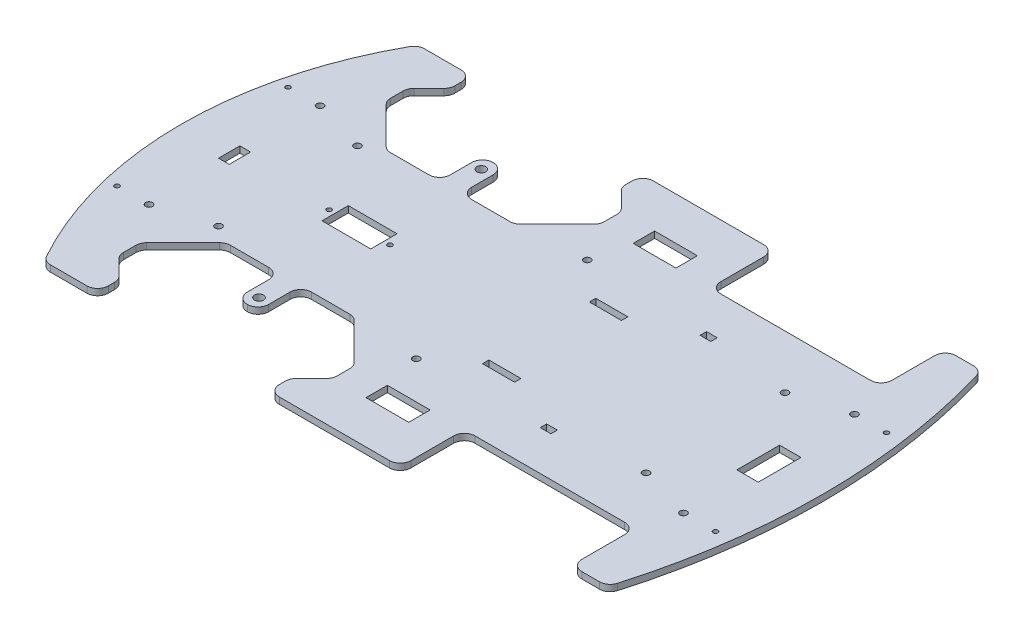
SolidWorks part; units mm, degrees
ref_plane "Front Plane" through (0, 0, 0) normal (0, 0, 1) x (1, 0, 0)
ref_plane "Top Plane" through (0, 0, 0) normal (0, 1, 0) x (1, 0, 0)
ref_plane "Right Plane" through (0, 0, 0) normal (1, 0, 0) x (0, 0, -1)
sketch "Sketch1" plane through (0, 0, 0) normal (0, 1, 0) x (1, 0, 0)
  line L1 (-150, -87.5) -> (150, -87.5) construction
  line L2 (-150, -87.5) -> (-150, 87.5) construction
  line L3 (-150, 87.5) -> (150, 87.5) construction
  line L4 (150, -87.5) -> (150, 87.5) construction
  line L5 (-150, -87.5) -> (150, 87.5) construction
  line L6 (-150, 87.5) -> (150, -87.5) construction
  line L7 (-91.537, 37.4826) -> (-31.537, 37.4826) construction
  line L9 (40, 87.5) -> (40, 57.5)
  line L10 (40, 57.5) -> (120, 57.5)
  line L11 (120, 57.5) -> (120, 87.5)
  line L12 (-150, 0) -> (150, 0) construction
  line L13 (-126.5544, 87.5) -> (-101.5544, 87.5)
  line L14 (120, -57.5) -> (120, -87.5)
  line L15 (-77.937, -6.15) -> (-55.137, -6.15)
  line L16 (-77.937, -6.15) -> (-77.937, 6.15)
  line L17 (-77.937, 6.15) -> (-55.137, 6.15)
  line L18 (-55.137, -6.15) -> (-55.137, 6.15)
  line L19 (-77.937, -6.15) -> (-55.137, 6.15) construction
  line L20 (-77.937, 6.15) -> (-55.137, -6.15) construction
  line L21 (40, -57.5) -> (120, -57.5)
  line L22 (40, -87.5) -> (40, -57.5)
  line L24 (-91.537, -37.4826) -> (-31.537, -37.4826) construction
  line L26 (-61.537, 37.4826) -> (-61.537, -37.4826) construction
  line L27 (-66.537, 6.15) -> (-66.537, -6.15) construction
  line L28 (-66.537, 37.4826) -> (-66.537, 57.4826)
  line L29 (-66.537, 57.4826) -> (-56.537, 57.4826)
  line L30 (-56.537, 57.4826) -> (-56.537, 37.4826)
  line L31 (-91.537, 37.4826) -> (-66.537, 37.4826)
  line L32 (-56.537, 37.4826) -> (-31.537, 37.4826)
  line L35 (-56.537, -57.4826) -> (-56.537, -37.4826)
  line L36 (-66.537, -57.4826) -> (-56.537, -57.4826)
  line L37 (-66.537, -37.4826) -> (-66.537, -57.4826)
  line L45 (80, 57.5) -> (80, -57.5) construction
  line L47 (40, 87.5) -> (-21.5544, 87.5)
  line L57 (-101.5544, 87.5) -> (-101.5544, 77.5)
  line L58 (-101.5544, 77.5) -> (-111.5544, 67.5)
  line L59 (-111.5544, 67.5) -> (-111.5544, 57.5)
  line L62 (-21.5544, 87.5) -> (-21.5544, 77.5)
  line L63 (-21.5544, 77.5) -> (-11.5544, 67.5)
  line L64 (-11.5544, 67.5) -> (-11.5544, 57.4651)
  line L65 (-11.5544, 57.4651) -> (-31.537, 37.4826)
  line L66 (-111.5544, 57.5) -> (-91.537, 37.4826)
  line L67 (-126.5544, -87.5) -> (-101.5544, -87.5)
  line L68 (-101.5544, -87.5) -> (-101.5544, -77.5)
  line L69 (-101.5544, -77.5) -> (-111.5544, -67.5)
  line L70 (-111.5544, -67.5) -> (-111.5544, -57.5)
  line L71 (-111.5544, -57.5) -> (-91.537, -37.4826)
  line L72 (-91.537, -37.4826) -> (-66.537, -37.4826)
  line L73 (-56.537, -37.4826) -> (-31.537, -37.4826)
  line L74 (-11.5544, -57.4651) -> (-31.537, -37.4826)
  line L75 (-11.5544, -67.5) -> (-11.5544, -57.4651)
  line L76 (-21.5544, -77.5) -> (-11.5544, -67.5)
  line L77 (-21.5544, -87.5) -> (-21.5544, -77.5)
  line L78 (40, -87.5) -> (-21.5544, -87.5)
  line L79 (120, -87.5) -> (136.956, -87.5)
  line L80 (120, 87.5) -> (136.956, 87.5)
  line L81 (56.9, -35.9) -> (61.9, -38.9) construction
  line L82 (56.9, 38.9) -> (61.9, 38.9)
  line L83 (56.9, 38.9) -> (56.9, 35.9)
  line L84 (56.9, 35.9) -> (61.9, 35.9)
  line L85 (61.9, 38.9) -> (61.9, 35.9)
  line L86 (56.9, 38.9) -> (61.9, 35.9) construction
  line L87 (56.9, 35.9) -> (61.9, 38.9) construction
  line L88 (56.9, -38.9) -> (61.9, -35.9) construction
  line L89 (61.9, -38.9) -> (61.9, -35.9)
  line L90 (56.9, -35.9) -> (61.9, -35.9)
  line L91 (56.9, -38.9) -> (56.9, -35.9)
  line L92 (56.9, -38.9) -> (61.9, -38.9)
  line L93 (0, 87.5) -> (0, -87.5) construction
  line L94 (17.5, -23.5) -> (32.5, -26.5) construction
  line L95 (120, -10) -> (130, -10)
  line L96 (120, -10) -> (120, 10)
  line L97 (120, 10) -> (130, 10)
  line L98 (130, -10) -> (130, 10)
  line L99 (120, -10) -> (130, 10) construction
  line L100 (120, 10) -> (130, -10) construction
  line L101 (17.5, 23.5) -> (32.5, 23.5)
  line L102 (17.5, 23.5) -> (17.5, 26.5)
  line L103 (17.5, 26.5) -> (32.5, 26.5)
  line L104 (32.5, 23.5) -> (32.5, 26.5)
  line L105 (17.5, 23.5) -> (32.5, 26.5) construction
  line L106 (17.5, 26.5) -> (32.5, 23.5) construction
  line L107 (17.5, -26.5) -> (32.5, -23.5) construction
  line L108 (17.5, -26.5) -> (32.5, -26.5)
  line L109 (32.5, -23.5) -> (32.5, -26.5)
  line L110 (17.5, -23.5) -> (32.5, -23.5)
  line L111 (17.5, -23.5) -> (17.5, -26.5)
  line L112 (4, -67.5) -> (24, -57.5) construction
  line L117 (4, 57.5) -> (24, 57.5)
  line L118 (4, 57.5) -> (4, 67.5)
  line L119 (4, 67.5) -> (24, 67.5)
  line L124 (24, 57.5) -> (24, 67.5)
  line L125 (4, 57.5) -> (24, 67.5) construction
  line L126 (4, 67.5) -> (24, 57.5) construction
  line L127 (4, -57.5) -> (24, -67.5) construction
  line L128 (4, -67.5) -> (24, -67.5)
  line L129 (24, -57.5) -> (24, -67.5)
  line L130 (4, -57.5) -> (24, -57.5)
  line L131 (4, -57.5) -> (4, -67.5)
  line L133 (-127.5, -5) -> (-122.5, -5)
  line L134 (-127.5, -5) -> (-127.5, 5)
  line L135 (-127.5, 5) -> (-122.5, 5)
  line L136 (-122.5, -5) -> (-122.5, 5)
  line L137 (-127.5, -5) -> (-122.5, 5) construction
  line L138 (-127.5, 5) -> (-122.5, -5) construction
  circle A0 centre (-80.787, 0) radius 1.1
  circle A1 centre (-52.287, 0) radius 1.1
  circle A3 centre (-61.537, 52) radius 2.1
  circle A4 centre (-61.537, -52) radius 2.1
  arc A7 (-126.5544, 87.5) -> (-126.5544, -87.5) centre (25, 0) ccw
  arc A10 (136.956, 87.5) -> (136.956, -87.5) centre (-150, 0) cw
  circle A11 centre (-100, 32.5) radius 1.6
  circle A12 centre (100, 32.5) radius 1.6
  circle A13 centre (100, -32.5) radius 1.6
  circle A14 centre (-100, -32.5) radius 1.6
  circle A15 centre (-125, -40) radius 1.6
  circle A16 centre (0, -40) radius 1.6
  circle A17 centre (125, -40) radius 1.6
  circle A18 centre (125, 40) radius 1.6
  circle A19 centre (0, 40) radius 1.6
  circle A20 centre (-125, 40) radius 1.6
  circle A21 centre (-140, 40) radius 1.1
  circle A22 centre (140, 40) radius 1.1
  circle A23 centre (-140, -40) radius 1.1
  circle A24 centre (140, -40) radius 1.1
  point P0 (0, 0)
  point P18 (-66.537, 0)
  point P53 (59.4, 37.4)
  point P79 (59.4, -37.4)
  point P101 (25, 25)
  point P103 (125, 0)
  point P111 (25, -25)
  point P116 (14, 62.5)
  point P127 (14, -62.5)
  point P134 (-125, 0)
  dimension "D15" = 2.2
  dimension "D19" = 4.2
  dimension "D21" = 20.6
  dimension "D23" = 32.5
  dimension "D24" = 175
  dimension "D26" = 100
  dimension "D28" = 80
  dimension "D34" = 300
  dimension "D22" = 3.2
  dimension "D27" = 3.2
  dimension "D41" = 3.2
  dimension "D43" = 3.2
  dimension "D50" = 20
  dimension "D51" = 10
  dimension "D54" = 2.2
  dimension "D1" = 175
  dimension "D2" = 300
  dimension "D3" = 25
  dimension "D4" = 10
  dimension "D5" = 135
  dimension "D6" = 135
  dimension "D7" = 80
  dimension "D8" = 30
  dimension "D9" = 25
  dimension "D10" = 30
  dimension "D11" = 10
  dimension "D12" = 22.8
  dimension "D13" = 12.3
  dimension "D14" = 6.4
  dimension "D16" = 2.85
  dimension "D17" = 20
  dimension "D18" = 10
  dimension "D20" = 52
  dimension "D25" = 10
  dimension "D29" = 10
  dimension "D30" = 135
  dimension "D31" = 10.0349
  dimension "D32" = 135
  dimension "D33" = 10
  dimension "D35" = 5
  dimension "D36" = 3
  dimension "D37" = 20.1
  dimension "D38" = 125
  dimension "D39" = 125
  dimension "D40" = 10
  dimension "D42" = 20
  dimension "D44" = 40
  dimension "D45" = 125
  dimension "D46" = 3
  dimension "D47" = 15
  dimension "D48" = 25
  dimension "D49" = 25
  dimension "D52" = 26
  dimension "D53" = 25
  dimension "D55" = 40
  dimension "D56" = 10
  dimension "D57" = 5
  dimension "D58" = 10
  dimension "D59" = 25
extrude "Boss-Extrude1" add sketch "Sketch1" along normal blind 3
fillet "Fillet1" radius 5 40 edges at (120, 1.5, 57.5) (120, 1.5, -57.5) (40, 1.5, -57.5) (40, 1.5, -87.5) (-21.5544, 1.5, -87.5) (40, 1.5, 57.5) (-56.537, 1.5, 37.4826) (-56.537, 1.5, 57.4826) (-66.537, 1.5, 57.4826) (-66.537, 1.5, 37.4826) (-56.537, 1.5, -37.4826) (-56.537, 1.5, -57.4826) (-66.537, 1.5, -57.4826) (-66.537, 1.5, -37.4826) (-91.537, 1.5, -37.4826) (-126.5544, 1.5, -87.5) (-126.5544, 1.5, 87.5) (40, 1.5, 87.5) (-21.5544, 1.5, 87.5) (-21.5544, 1.5, 77.5) (-11.5544, 1.5, 67.5) (-11.5544, 1.5, 57.4651) (-31.537, 1.5, 37.4826) (-91.537, 1.5, 37.4826) (-111.5544, 1.5, 67.5) (-111.5544, 1.5, 57.5) (-101.5544, 1.5, 77.5) (-101.5544, 1.5, 87.5) (-21.5544, 1.5, -77.5) (-11.5544, 1.5, -67.5) (-11.5544, 1.5, -57.4651) (-31.537, 1.5, -37.4826) (-111.5544, 1.5, -57.5) (-111.5544, 1.5, -67.5) (-101.5544, 1.5, -77.5) (-101.5544, 1.5, -87.5) (120, 1.5, -87.5) (136.956, 1.5, -87.5) (136.956, 1.5, 87.5) (120, 1.5, 87.5)
